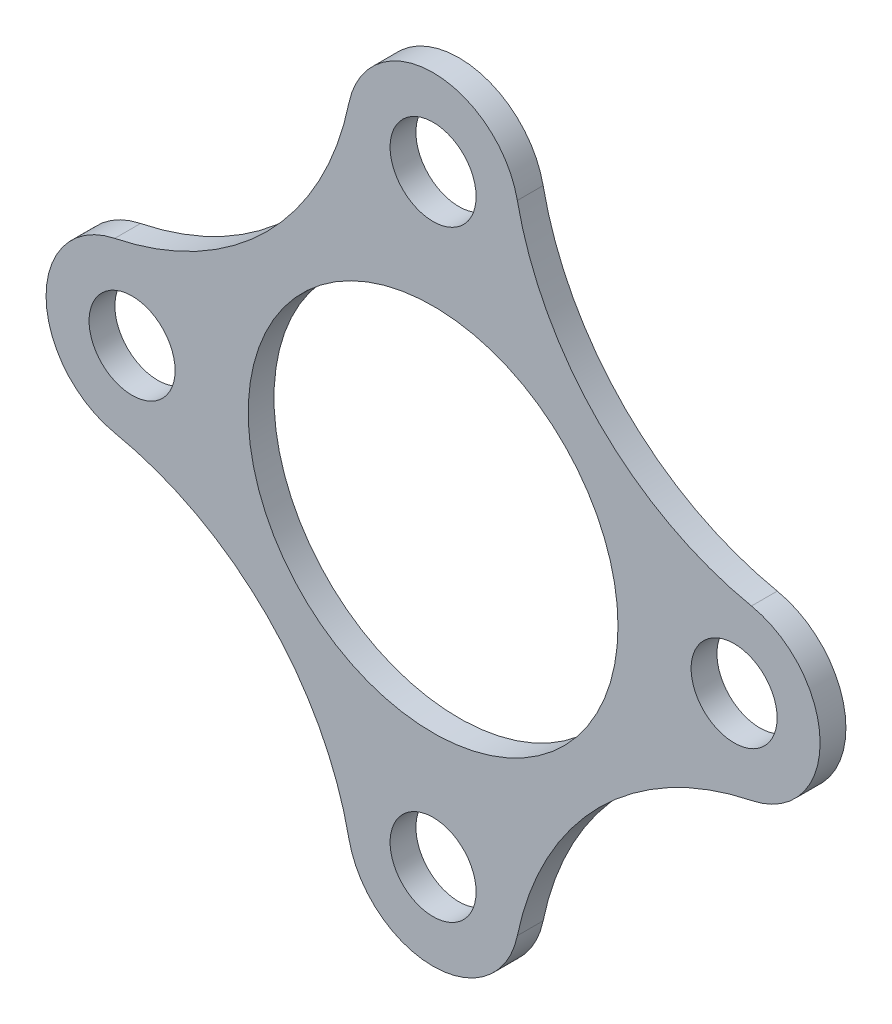
SolidWorks part; units mm, degrees
ref_plane "Płaszczyzna przednia" through (0, 0, 0) normal (0, 0, 1) x (1, 0, 0)
ref_plane "Płaszczyzna górna" through (0, 0, 0) normal (0, 1, 0) x (1, 0, 0)
ref_plane "Płaszczyzna prawa" through (0, 0, 0) normal (1, 0, 0) x (0, 0, -1)
sketch "Szkic1" plane through (0, 0, 0) normal (0, 0, 1) x (1, 0, 0)
  arc A1 (21.5, 0) -> (-21.5, 0) centre (0, 0) ccw
  circle A3 centre (0, 35) radius 5
  arc A4 (10, 35) -> (-10, 35) centre (0, 35) ccw
  circle A7 centre (0, 0) radius 21.5
  arc A8 (35, -10) -> (35, 10) centre (35, 0) ccw
  circle A9 centre (35, 0) radius 5
  arc A10 (-10, -35) -> (10, -35) centre (0, -35) ccw
  circle A11 centre (0, -35) radius 5
  arc A12 (-35, 10) -> (-35, -10) centre (-35, 0) ccw
  circle A13 centre (-35, 0) radius 5
  arc A14 (-10, -35) -> (-35, -10) centre (-35, -35) ccw
  arc A15 (10, -35) -> (35, -10) centre (35, -35) cw
  arc A16 (35, 10) -> (10, 35) centre (35, 35) cw
  arc A17 (-35, 10) -> (-10, 35) centre (-35, 35) ccw
  dimension "D1" = 43
  dimension "D2" = 35
  dimension "D3" = 20
  dimension "D4" = 10
  dimension "D5" = 4
extrude "Dodanie-wyciągnięcie1" add sketch "Szkic1" along normal blind 3 contours A4 | A12 | A12 | A4 | A8 | A8 | A17 A12 A14 A10 A15 A8 A16 A4 A13 A11 A9 A7 A1 A3 region at (16.4223, 16.4223, 0)
sketch "Szkic2" plane through (0, 0, 0) normal (0, 0, 1) x (1, 0, 0)
  line L4 (37.0167, -9.7945) -> (25.0125, -7.2377)
  line L5 (25.0125, -7.2377) -> (6.5278, -26.0865)
  line L6 (6.5278, -26.0865) -> (9.7945, -37.0167)
  line L7 (-9.7945, -37.0167) -> (-6.1039, -26.0865)
  line L8 (-6.1039, -26.0865) -> (-27.7279, -4.8802)
  line L9 (-27.7279, -4.8802) -> (-37.0167, -9.7945)
  line L10 (-37.0167, 9.7945) -> (-28.7756, 5.7222)
  line L11 (-28.7756, 5.7222) -> (-5.4688, 25.9791)
  line L12 (-5.4688, 25.9791) -> (-9.7945, 37.0167)
  line L13 (9.7945, 37.0167) -> (8.1612, 24.7853)
  line L14 (8.1612, 24.7853) -> (27.5997, 5.7222)
  line L15 (27.5997, 5.7222) -> (37.0167, 9.7945)
  arc A0 (-9.7945, -37.0167) -> (-37.0167, -9.7945) centre (-44.0754, -44.0754) ccw
  arc A1 (-10, -35) -> (10, -35) centre (0, -35) ccw construction
  arc A2 (-35, 10) -> (-35, -10) centre (-35, 0) ccw construction
  arc A3 (9.7945, -37.0167) -> (37.0167, -9.7945) centre (44.0754, -44.0754) cw
  arc A4 (35, -10) -> (35, 10) centre (35, 0) ccw construction
  arc A5 (37.0167, 9.7945) -> (9.7945, 37.0167) centre (44.0754, 44.0754) cw
  arc A6 (10, 35) -> (-10, 35) centre (0, 35) ccw construction
  arc A7 (-9.7945, 37.0167) -> (-37.0167, 9.7945) centre (-44.0754, 44.0754) cw
  dimension "D1" = 35
extrude "Dodanie-wyciągnięcie2" add sketch "Szkic2" along normal up to surface (3 mm away) contours L15 A5 L13 L14 | L12 A7 L10 L11 | A0 L7 L8 L9 | A3 L4 L5 L6 region at (-19.064, -18.0882, 0) region at (-18.3516, 19.0415, 0) region at (19.8156, 17.6984, 0) up to face at (0, 0, 3)
